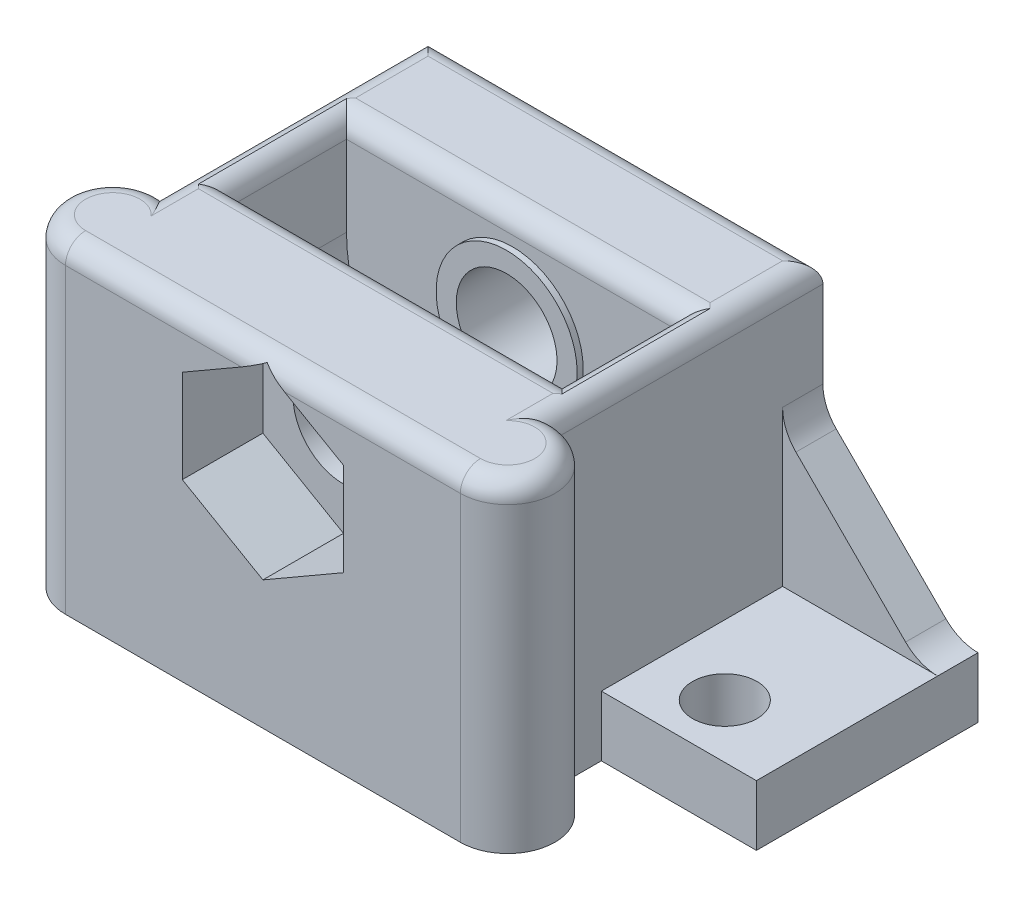
SolidWorks part; units mm, degrees
ref_plane "Front Plane" through (0, 0, 0) normal (0, 0, 1) x (1, 0, 0)
ref_plane "Top Plane" through (0, 0, 0) normal (0, 1, 0) x (1, 0, 0)
ref_plane "Right Plane" through (0, 0, 0) normal (1, 0, 0) x (0, 0, -1)
sketch "Sketch1" plane through (0, 0, 0) normal (0, 1, 0) x (1, 0, 0)
  line L0 (0, 0) -> (19.6, 0)
  line L1 (0, 4.7) -> (0, 18)
  line L2 (0, 18) -> (19.6, 18)
  line L3 (19.6, 18) -> (19.6, 4.7)
  arc A0 (0, 4.7) -> (0, 0) centre (0, 2.35) ccw
  arc A1 (19.6, 0) -> (19.6, 4.7) centre (19.6, 2.35) ccw
  dimension "D1" = 4.7
  dimension "D2" = 18
  dimension "D3" = 19.6
extrude "Boss-Extrude1" add sketch "Sketch1" along normal blind 16
sketch "Sketch5" plane through (0, 0, 0) normal (0, 0, 1) x (1, 0, 0)
  line L0 (0, 0) -> (19.6, 0) construction
  line L1 (1.55, 11) -> (1.55, 16)
  line L2 (0, 16) -> (19.6, 16) construction
  line L3 (18.05, 11) -> (18.05, 16)
  line L4 (1.55, 16) -> (18.05, 16)
  line L5 (9.8, 0) -> (9.8, 1.0251) construction
  arc A0 (1.55, 11) -> (18.05, 11) centre (9.8, 11) ccw
  dimension "D1" = 11
  dimension "D2" = 16.5
extrude "Cut-Extrude4" cut sketch "Sketch5" against normal blind 5.8 from offset 6.6 offset against normal yes
sketch "Sketch6" plane through (0, 0, -18) normal (0, 0, -1) x (-1, 0, 0)
  circle A0 centre (-9.8, 11) radius 2.5
  dimension "D1" = 5
extrude "Cut-Extrude5" cut sketch "Sketch6" against normal up to surface (18 mm away) up to face at (9.8, 8, 0)
sketch "Sketch7" plane through (0, 0, 0) normal (0, 0, 1) x (1, 0, 0)
  line L1 (9.8, 15.6188) -> (5.8, 13.3094)
  line L2 (5.8, 13.3094) -> (5.8, 8.6906)
  line L3 (5.8, 8.6906) -> (9.8, 6.3812)
  line L4 (9.8, 6.3812) -> (13.8, 8.6906)
  line L5 (13.8, 8.6906) -> (13.8, 13.3094)
  line L6 (13.8, 13.3094) -> (9.8, 15.6188)
  circle A0 centre (9.8, 11) radius 4 construction
  dimension "D1" = 8
extrude "Cut-Extrude6" cut sketch "Sketch7" against normal blind 4
sketch "Sketch8" plane through (0, 0, -12.4) normal (0, 0, 1) x (1, 0, 0)
  circle A0 centre (9.8, 11) radius 2.5
  circle A1 centre (9.8, 11) radius 2.5 construction
  circle A2 centre (9.8, 11) radius 3.5
  dimension "D1" = 7
extrude "Boss-Extrude2" add sketch "Sketch8" along normal blind 0.3
ref_plane "Plane1" through (0, 0, -9.5) normal (0, 0, 1) x (1, 0, 0)
mirror "Mirror1" about plane through (0, 0, -9.5) normal (0, 0, 1) of "Boss-Extrude2"
sketch "Sketch9" plane through (0, 0, 0) normal (0, -1, 0) x (1, 0, 0)
  line L0 (-7.7, -7) -> (0, -7)
  line L2 (-7.7, -7) -> (-7.7, -18)
  line L3 (27.3, -18) -> (19.6, -18)
  line L4 (27.3, -18) -> (27.3, -7)
  line L5 (0, -18) -> (-7.7, -18)
  line L7 (0, -18) -> (0, -4.7) construction
  line L8 (0, -7) -> (0, -18)
  line L10 (19.6, -18) -> (19.6, -7)
  line L11 (19.6, -4.7) -> (19.6, -18) construction
  line L12 (19.6, -7) -> (27.3, -7)
  line L13 (0, 0) -> (19.6, 0) construction
  dimension "D2" = 35
  dimension "D3" = 7
extrude "Boss-Extrude3" add sketch "Sketch9" against normal blind 3
sketch "Sketch10" plane through (0, 3, 0) normal (0, 1, 0) x (1, 0, 0)
  line L0 (27.3, 18) -> (27.3, 7) construction
  line L1 (9.8, 0) -> (9.8, 1.9073) construction
  line L2 (27.3, 7) -> (19.6, 7) construction
  circle A0 centre (-3.45, 9.68) radius 1.6
  circle A1 centre (23.05, 9.68) radius 1.6
  dimension "D1" = 3.2
  dimension "D2" = 4.25
  dimension "D3" = 2.68
extrude "Cut-Extrude7" cut sketch "Sketch10" against normal up to next and the other way through all
sketch "Sketch12" plane through (0, 0, -18) normal (0, 0, -1) x (-1, 0, 0)
  line L0 (-19.6, 3) -> (-27.3, 3)
  line L1 (-19.6, 3) -> (-19.6, 10.7)
  line L2 (-19.6, 16) -> (-19.6, 3) construction
  line L3 (0, 10.7) -> (0, 3)
  line L4 (0, 16) -> (0, 3) construction
  line L5 (0, 3) -> (7.7, 3)
  line L6 (-20.2606, 9.1053) -> (-25.7053, 3.6606)
  line L7 (-19.6, 16) -> (-19.6, 0) construction
  line L8 (-9.8, 0) -> (-9.8, 3) construction
  line L9 (-27.3, 0) -> (7.7, 0) construction
  line L10 (0.6606, 9.1053) -> (6.1053, 3.6606)
  arc A0 (-19.6, 10.7) -> (-20.2606, 9.1053) centre (-21.8553, 10.7) cw
  arc A1 (-25.7053, 3.6606) -> (-27.3, 3) centre (-27.3, 5.2553) cw
  arc A2 (6.1053, 3.6606) -> (7.7, 3) centre (7.7, 5.2553) ccw
  arc A3 (0, 10.7) -> (0.6606, 9.1053) centre (2.2553, 10.7) ccw
extrude "Boss-Extrude4" add sketch "Sketch12" against normal blind 2
fillet "Fillet1" radius 1 10 edges at (9.8, 16, -6.6) (18.05, 16, -9.5) (9.8, 16, -12.4) (1.55, 16, -9.5) (0, 16, -11.35) (9.8, 16, -18) (19.6, 16, -11.35) (21.95, 16, -2.35) (9.8, 16, 0) (-2.35, 16, -2.35)
